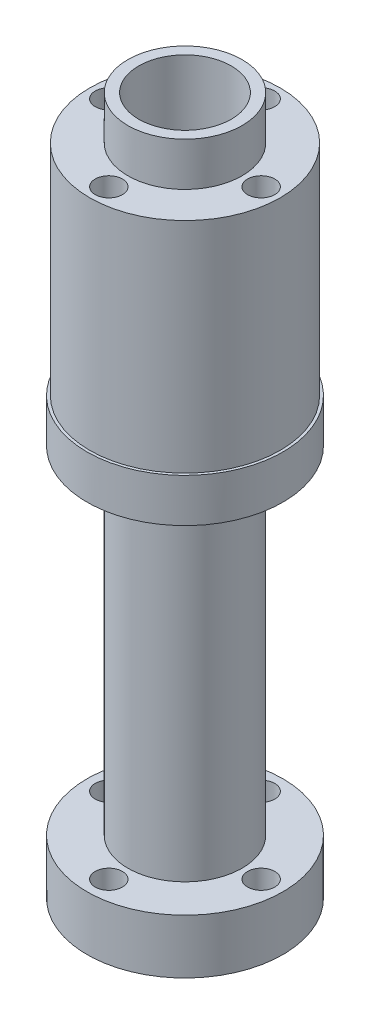
SolidWorks part; units mm, degrees
other "细节项目1"
other "细节项目2"
material "6061-T6 (SS)"
ref_plane "前视基准面" through (0, 0, 0) normal (0, 0, 1) x (1, 0, 0)
ref_plane "上视基准面" through (0, 0, 0) normal (0, 1, 0) x (1, 0, 0)
ref_plane "右视基准面" through (0, 0, 0) normal (1, 0, 0) x (0, 0, -1)
sketch "草图1" plane through (0, 0, 0) normal (0, 0, 1) x (1, 0, 0)
  line L0 (0, 0) -> (0, 22.2724) construction
  line L1 (-9, 36) -> (-5.25, 36)
  line L2 (-4.25, 0) -> (-9, 0)
  line L3 (-4.25, 0) -> (-4.25, 60.1)
  line L4 (-4.25, 60.1) -> (-9, 60.1)
  line L5 (-9, 0) -> (-9, 5)
  line L6 (-5.25, 36) -> (-5.25, 5)
  line L7 (-5.25, 5) -> (-9, 5)
  line L8 (-9, 36) -> (-9, 60.1)
  dimension "D1" = 8.5
  dimension "D2" = 18
  dimension "D3" = 60.1
  dimension "D4" = 36
  dimension "D5" = 5
  dimension "D6" = 1
revolve "旋转1" add sketch "草图1" angle 360 about L0
sketch "草图2" plane through (0, 60.1, 0) normal (0, 1, 0) x (1, 0, 0)
  circle A0 centre (0, 0) radius 7 construction
  circle A1 centre (0, 7) radius 1.25
  circle A2 centre (0, -7) radius 1.25
  circle A3 centre (-7, 0) radius 1.25
  circle A4 centre (7, 0) radius 1.25
  dimension "D1" = 14
  dimension "D2" = 2.5
extrude "切除-拉伸1" cut sketch "草图2" against normal blind 10
cosmetic thread "装饰螺纹线3" parameters "D2"=3
cosmetic thread "装饰螺纹线4" parameters "D2"=3
cosmetic thread "装饰螺纹线5" parameters "D2"=3
cosmetic thread "装饰螺纹线6" parameters "D2"=3
extrude "切除-拉伸2" cut sketch "草图2<2>" along normal blind 6 from surface starting at face at (0, 0, -4.25)
sketch "草图2<2>" plane through (0, 60.1, 0) normal (0, 1, 0) x (1, 0, 0) same geometry as "草图2"
cosmetic thread "装饰螺纹线1" parameters "D2"=3
cosmetic thread "装饰螺纹线2" parameters "D2"=3
sketch "草图3" plane through (0, 60.1, 0) normal (0, 1, 0) x (1, 0, 0)
  circle A0 centre (0, 0) radius 8.75
  dimension "D1" = 17.5
extrude "切除-拉伸3" cut sketch "草图3" against normal offset from surface (20.1 mm away) 4 flip side to cut up to face at (0, 36, -5.25)
sketch "草图4" plane through (0, 60.1, 0) normal (0, 1, 0) x (1, 0, 0)
  circle A0 centre (0, 0) radius 5.25
  circle A1 centre (0, 0) radius 4.25 construction
  circle A2 centre (0, 0) radius 4.25
  dimension "D1" = 10.5
extrude "凸台-拉伸1" add sketch "草图4" along normal blind 4
